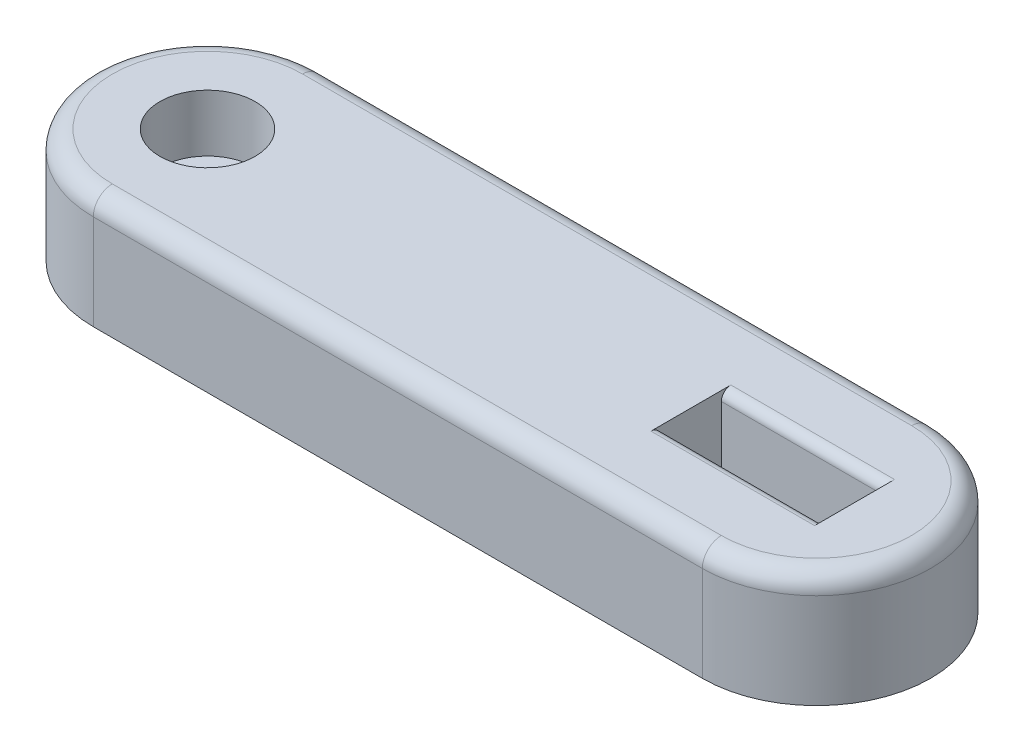
SolidWorks part; units mm, degrees
material "PET"
ref_plane "Front Plane" through (0, 0, 0) normal (0, 0, 1) x (1, 0, 0)
ref_plane "Top Plane" through (0, 0, 0) normal (0, 1, 0) x (1, 0, 0)
ref_plane "Right Plane" through (0, 0, 0) normal (1, 0, 0) x (0, 0, -1)
sketch "Sketch1" plane through (0, 0, 0) normal (0, 1, 0) x (1, 0, 0)
  line L0 (0, 0) -> (203.2, 0) construction
  line L1 (0, 38.1) -> (203.2, 38.1)
  line L2 (0, -38.1) -> (203.2, -38.1)
  arc A0 (0, 38.1) -> (0, -38.1) centre (0, 0) ccw
  arc A1 (203.2, -38.1) -> (203.2, 38.1) centre (203.2, 0) ccw
  point P3 (101.6, 0)
  dimension "D2" = 38.1
  dimension "D1" = 203.2
extrude "Boss-Extrude1" add sketch "Sketch1" along normal blind 38.1
sketch "Sketch2" plane through (0, 38.1, 0) normal (0, 1, 0) x (1, 0, 0)
  line L0 (101.6, 38.1) -> (101.6, -38.1) construction
  line L1 (203.2, 38.1) -> (0, 38.1) construction
  line L2 (0, -38.1) -> (203.2, -38.1) construction
  circle A0 centre (0, 0) radius 15.875
  dimension "D1" = 31.75
extrude "Cut-Extrude1" cut sketch "Sketch2" against normal blind 19.05 contours A0
sketch "Sketch3" plane through (0, 0, 0) normal (0, -1, 0) x (1, 0, 0)
  circle A0 centre (0, 0) radius 12.7
  dimension "D1" = 25.4
extrude "Boss-Extrude2" add sketch "Sketch3" along normal blind 3.175 contours A0
sketch "Sketch4" plane through (0, 19.05, 0) normal (0, 1, 0) x (1, 0, 0)
  circle A0 centre (0, 0) radius 7.9375 construction
  circle A1 centre (0, 7.9375) radius 2.159
  dimension "D1" = 4.318
  dimension "D2" = 15.875
extrude "Cut-Extrude3" cut sketch "Sketch4" against normal up to surface (22.225 mm away) contours A1 up to face at (0, -3.175, -12.7)
pattern_circular "CirPattern1" count 4 over 360 about axis through (0, 19.05, 0) along (0, 1, 0) of "Cut-Extrude3"
ref_plane "Plane1" through (76.2, 0, 0) normal (1, 0, 0) x (0, 0, -1)
fillet "Fillet3" radius 6.35 4 edges at (-38.1, 38.1, 0) (101.6, 38.1, -38.1) (241.3, 38.1, 0) (101.6, 38.1, 38.1)
sketch "Sketch6" plane through (0, 38.1, 0) normal (0, 1, 0) x (1, 0, 0)
  line L0 (161.29, 10.16) -> (215.9, 10.16)
  line L1 (215.9, 10.16) -> (215.9, -10.16)
  line L2 (215.9, -10.16) -> (161.29, -10.16)
  line L3 (161.29, -10.16) -> (161.29, 10.16)
  circle A0 centre (203.2, 0) radius 9.525
  point P5 (215.9, 0)
  dimension "D1" = 20.32
  dimension "D3" = 19.05
  dimension "D2" = 54.61
  dimension "D4" = 12.7
extrude "Cut-Extrude5" cut sketch "Sketch6" against normal up to surface (38.1 mm away) contours A0 up to face at (0, 0, 12.7)
extrude "Cut-Extrude6" cut sketch "Sketch6<3>" against normal offset from surface (34.925 mm away) 3.175 up to face at (203.2, 0, 9.525)
sketch "Sketch6<3>" plane through (0, 38.1, 0) normal (0, 1, 0) x (1, 0, 0) same geometry as "Sketch6"
fillet "Fillet4" radius 3.175 3 edges at (188.595, 38.1, -10.16) (188.595, 38.1, 10.16) (203.2, 3.175, 9.525)
